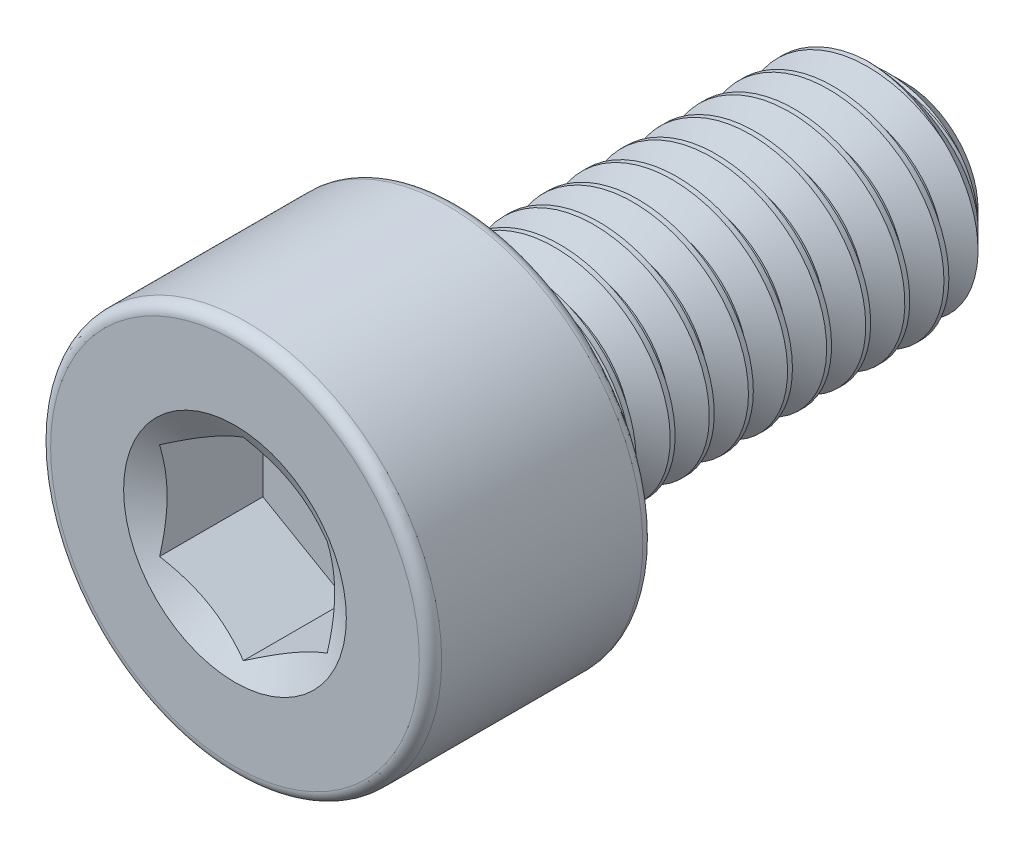
SolidWorks part; units mm, degrees
ref_plane "Front Plane" through (0, 0, 0) normal (0, 0, 1) x (1, 0, 0)
ref_plane "Top Plane" through (0, 0, 0) normal (0, 1, 0) x (1, 0, 0)
ref_plane "Right Plane" through (0, 0, 0) normal (1, 0, 0) x (0, 0, -1)
sketch "Sketch1" plane through (0, 0, 0) normal (1, 0, 0) x (0, 0, -1)
  line L0 (6, 0) -> (-6, 0) construction
  line L1 (-2, 3.5) -> (-2, -3.5) construction
  line L2 (6, 2) -> (6, -2) construction
  line L3 (5.9563, 2.0758) -> (6.3063, 1.4696) construction
  line L4 (6.2625, 1.5453) -> (6.35, 1.5453) construction
  line L5 (6.3063, 1.4696) -> (6.6563, 2.0758) construction
  line L6 (6.6563, 2.0758) -> (5.9563, 2.0758) construction
  line L7 (6.3063, 1.5453) -> (6.3063, 1.4696) construction
  line L8 (6.3063, 2.0758) -> (6.3063, 2) construction
  line L9 (6.6125, 2) -> (6, 2) construction
  point P4 (-2, 0)
  point P6 (-2, 1.5)
  point P7 (4.25, -2)
  point P20 (6.3063, 2.0379)
  dimension "Head Height" = 4
  dimension "Head Diameter" = 7
  dimension "Drive Size" = 3
  dimension "Length" = 8
  dimension "Thread Size" = 4
  dimension "Thread Pitch" = 0.7
  dimension "Pitch/8" = 0.0875
  dimension "Thread Note" = 1.75
sketch "Sketch2" plane through (0, 0, 0) normal (1, 0, 0) x (0, 0, -1)
  line L0 (6, 0) -> (6, 1.3)
  line L1 (6, 2) -> (6, -2) construction
  line L2 (6, 1.3) -> (5.3, 2)
  line L3 (5.3, 2) -> (-2, 2)
  line L4 (-2, 2) -> (-2, 3.3)
  line L5 (-2.2, 3.5) -> (-5.8, 3.5)
  line L6 (-6, 3.3) -> (-6, 0)
  line L7 (6, 0) -> (-6, 0) construction
  line L8 (-6, 0) -> (6, 0)
  arc A0 (-2, 3.3) -> (-2.2, 3.5) centre (-2.2, 3.3) ccw
  arc A1 (-5.8, 3.5) -> (-6, 3.3) centre (-5.8, 3.3) ccw
  point P19 (-2, 3.5)
  dimension "D3" = 0.2
  dimension "D1" = 0.7
  dimension "D2" = 45
revolve "Revolve1" add sketch "Sketch2" angle 360 about L0
sketch "Sketch3" plane through (0, 0, 0) normal (0, 0, 1) x (1, 0, 0)
  line L1 (-1.5, 0.866) -> (-1.5, -0.866)
  line L2 (-1.5, -0.866) -> (0, -1.7321)
  line L3 (0, -1.7321) -> (1.5, -0.866)
  line L4 (1.5, -0.866) -> (1.5, 0.866)
  line L5 (1.5, 0.866) -> (0, 1.7321)
  line L6 (0, 1.7321) -> (-1.5, 0.866)
  circle A0 centre (0, 0) radius 1.5 construction
  circle A1 centre (0, 0) radius 3.5 construction
extrude "Cut-Extrude1" cut sketch "Sketch3" against normal blind 2 from vertex starting at point (0, 0, 6)
sketch "Sketch4" plane through (0, 0, 6) normal (0, 0, 1) x (1, 0, 0)
  line L0 (0, 1.7321) -> (0, 2.2547) construction
  line L1 (0, 2.2547) -> (0, 2.7774) construction
  line L2 (0, 2.7774) -> (0, 3.3) construction
  circle A0 centre (0, 0) radius 1.9934
  point P12 (0, 1.9934)
extrude "Cut-Extrude2" cut sketch "Sketch4" against normal through all draft 60
split "Split1" bodies to split 106 112 resulting bodies 107 108 split by face at (-3.3, 0, 2)
sketch "Sketch5" plane through (0, 0, 0) normal (1, 0, 0) x (0, 0, -1)
  line L0 (6.2625, 1.5453) -> (6.35, 1.5453)
  line L1 (6.35, 1.5453) -> (6.6344, 2.0379)
  line L2 (6.6344, 2.0379) -> (5.9781, 2.0379)
  line L3 (5.9781, 2.0379) -> (6.2625, 1.5453)
  line L4 (5.9563, 2.0758) -> (6.3063, 1.4696) construction
sketch "Sketch6" plane through (0, 0, -6) normal (0, 0, -1) x (-1, 0, 0)
  circle A0 centre (0, 0) radius 2
curve "Helix/Spiral1" pitch 0.7 height 8.7 radius 2 centre (0, 0, -6) axis (0, 0, 1) start towards (0, 1, 0)
sweep "Cut-Sweep1" cut profiles "Sketch5" path "Helix/Spiral1" align with end faces yes
sketch "Sketch7" plane through (0, 0, 2) normal (0, 0, -1) x (-1, 0, 0)
  circle A0 centre (0, 0) radius 2.0508
  circle A1 centre (0, 0) radius 2 construction
  dimension "D1" = 0.0508
extrude "Boss-Extrude1" add sketch "Sketch7" along normal blind 2.1 draft 20 and the other way blind 0.4
equation "\"Pitch/8@Sketch1\" = \"Thread Pitch@Sketch1\" / 8"
equation "\"Thread Note@Sketch1\" = \"Thread Pitch@Sketch1\" * 2.5"
equation "\"D1@Sketch2\" = \"Thread Pitch@Sketch1\""
equation "\"D3@Sketch2\"=\"Head Height@Sketch1\"*.05"
equation "\"D1@Cut-Extrude1\" = \"Head Height@Sketch1\" * .5"
equation "\"D3@Helix/Spiral1\" = \"Length@Sketch1\" + \"Thread Pitch@Sketch1\""
equation "\"D4@Helix/Spiral1\" = \"Thread Pitch@Sketch1\""
equation "\"D2@Boss-Extrude1\" = \"Head Height@Sketch1\" * .1"
equation "\"D1\"= \"Thread Size@Sketch1\" * .4"
equation "\"D1@Boss-Extrude1\" = \"Thread Pitch@Sketch1\" * 3"
